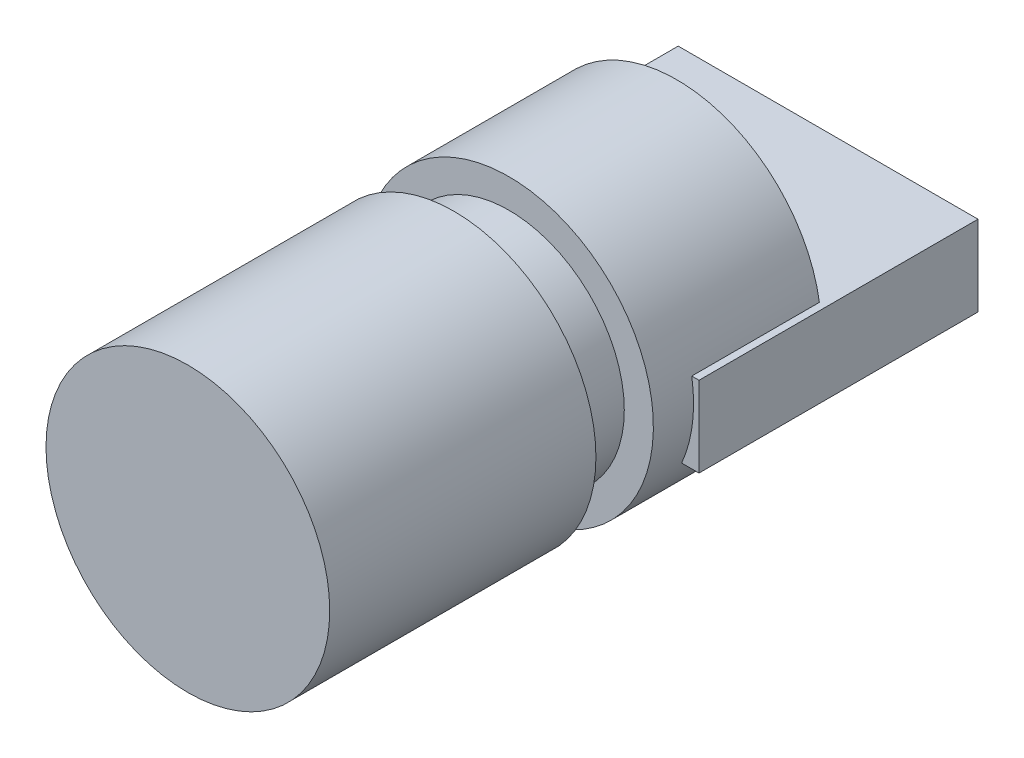
SolidWorks part; units mm, degrees
ref_plane "Front Plane" through (0, 0, 0) normal (0, 0, 1) x (1, 0, 0)
ref_plane "Top Plane" through (0, 0, 0) normal (0, 1, 0) x (1, 0, 0)
ref_plane "Right Plane" through (0, 0, 0) normal (1, 0, 0) x (0, 0, -1)
sketch "Sketch3" plane through (0, 0, 0) normal (0, 0, 1) x (1, 0, 0)
  circle A0 centre (-7.6717, 4.7989) radius 3
  dimension "D1" = 6
extrude "Boss-Extrude1" add sketch "Sketch3" along normal blind 5.63
sketch "Sketch8" plane through (0, 0, 0) normal (0, 0, -1) x (-1, 0, 0)
  circle A0 centre (7.6717, 4.7989) radius 2.44
  circle A1 centre (7.6717, 4.7989) radius 3 construction
  dimension "D1" = 4.88
extrude "Boss-Extrude2" add sketch "Sketch8" along normal blind 1.16
sketch "Sketch9" plane through (0, 0, -1.16) normal (0, 0, -1) x (-1, 0, 0)
  circle A0 centre (7.6717, 4.7989) radius 3.055
  circle A1 centre (7.6717, 4.7989) radius 2.44 construction
  dimension "D1" = 6.11
extrude "Boss-Extrude3" add sketch "Sketch9" along normal blind 3.55
sketch "Sketch12" plane through (0, 0, 5.63) normal (0, 0, 1) x (1, 0, 0)
  line L0 (-10.6717, 4.7989) -> (-4.6717, 4.7989) construction
  line L1 (-7.6717, 7.7989) -> (-7.6717, 1.7989) construction
  circle A0 centre (-7.6717, 4.7989) radius 3 construction
sketch "Sketch13" plane through (0, 0, -4.71) normal (0, 0, -1) x (-1, 0, 0)
  line L0 (4.6167, 4.7989) -> (10.7267, 4.7989) construction
  line L1 (7.6717, 7.8539) -> (7.6717, 1.7439) construction
  circle A0 centre (7.6717, 4.7989) radius 3.055 construction
ref_plane "Horizontal Plane" through (0, 4.7989, 0) normal (0, 1, 0) x (1, 0, 0)
ref_plane "Face Plane" through (0, 0, 5.63) normal (0, 0, 1) x (1, 0, 0)
ref_plane "Vertical Plane" through (-7.6717, 0, 0) normal (-1, 0, 0) x (0, 0, 1)
sketch "Sketch15" plane through (0, 4.7989, 0) normal (0, 1, 0) x (1, 0, 0)
  line L1 (-10.7267, 1.16) -> (-4.6167, 1.16) construction
  line L2 (-10.8417, 2.01) -> (-4.5017, 2.01)
  line L3 (-10.8417, 2.01) -> (-10.8417, 7.91)
  line L4 (-10.8417, 7.91) -> (-4.5017, 7.91)
  line L6 (-4.5017, 2.01) -> (-4.5017, 7.91)
  line L7 (-10.8417, 2.01) -> (-4.5017, 7.91) construction
  line L8 (-10.8417, 7.91) -> (-4.5017, 2.01) construction
  line L9 (-4.6167, 4.71) -> (-10.7267, 4.71) construction
  point P0 (-7.6717, 4.96)
  point P12 (-7.6717, 4.71)
  dimension "D1" = 5.9
  dimension "D2" = 6.34
  dimension "D3" = 6.75
extrude "Boss-Extrude4" add sketch "Sketch15" against normal blind 1.7 from offset 0.485 contours L2 L6 L4 L3 | L4 L6 L2 L3 region at (-7.6717, 4.7989, -4.96)
